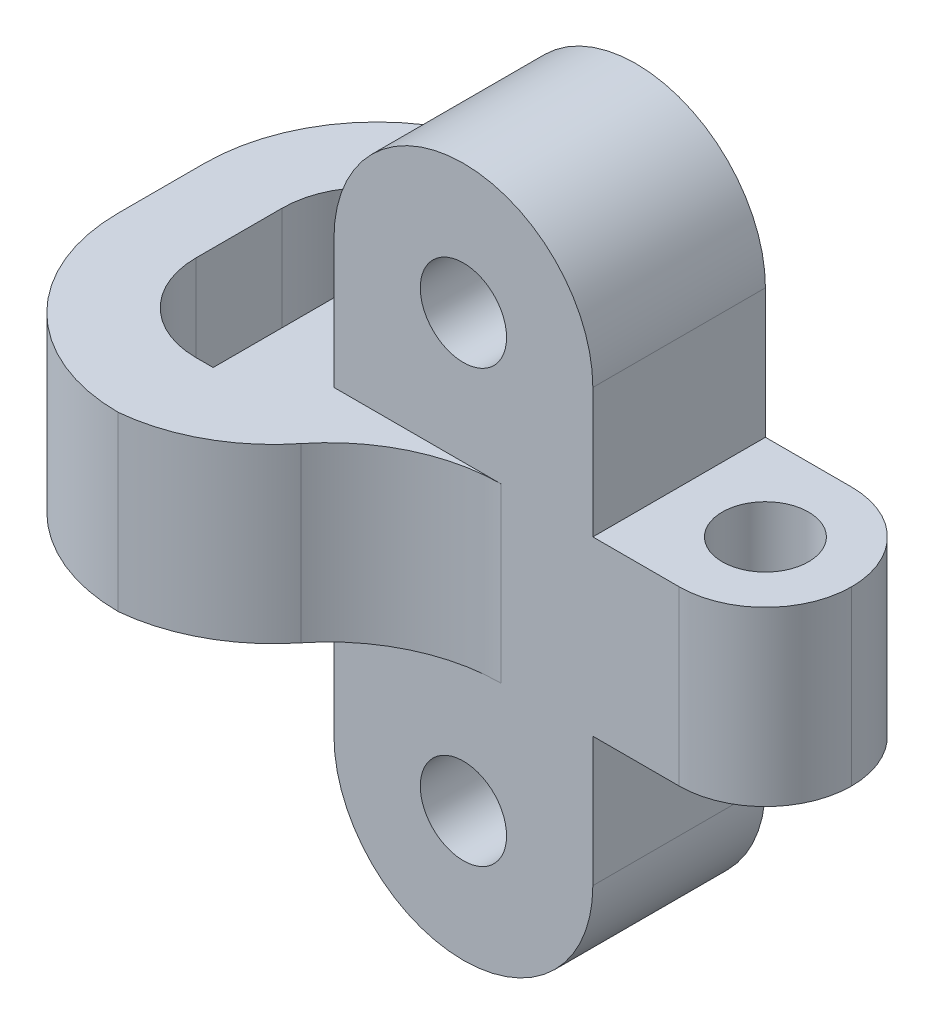
SolidWorks part; units mm, degrees
ref_plane "前视基准面" through (0, 0, 0) normal (0, 0, 1) x (1, 0, 0)
ref_plane "上视基准面" through (0, 0, 0) normal (0, 1, 0) x (1, 0, 0)
ref_plane "右视基准面" through (0, 0, 0) normal (1, 0, 0) x (0, 0, -1)
other "Configuration Table"
sketch "Sketch1" plane through (0, 0, 0) normal (0, 0, 1) x (1, 0, 0)
  line L0 (0, 0) -> (0, 25) construction
  line L1 (7.5, 25) -> (7.5, 0)
  line L2 (-7.5, 25) -> (-7.5, 0)
  circle A0 centre (0, 0) radius 2.5
  circle A1 centre (0, 0) radius 7.5
  circle A2 centre (0, 25) radius 2.5
  circle A3 centre (0, 25) radius 7.5
  point P10 (-7.5, 0)
  dimension "D1" = 15
  dimension "D2" = 5
  dimension "D3" = 25
extrude "Boss-Extrude1" add sketch "Sketch1" along normal mid plane 10 contours A1 L0 A3 L2 | L0 A1 L1 A3 | A0 A1 | A3 A2 region at (5.1533, 5.1533, 0) region at (-4.2552, 12.5, 0) region at (4.2552, 12.5, 0) region at (-5.1533, 19.8467, 0)
sketch "Sketch2" plane through (-7.5, 0, 0) normal (-1, 0, 0) x (0, 0, 1)
  line L0 (0, 25) -> (0, 0) construction
  line L1 (5, 25) -> (-5, 25) construction
  line L2 (0, 0) -> (0, 12.5) construction
  line L4 (-12.5, 7.5) -> (12.5, 7.5)
  line L5 (-12.5, 7.5) -> (-12.5, 17.5)
  line L6 (-12.5, 17.5) -> (12.5, 17.5)
  line L7 (12.5, 7.5) -> (12.5, 17.5)
  line L8 (-12.5, 7.5) -> (12.5, 17.5) construction
  line L9 (-12.5, 17.5) -> (12.5, 7.5) construction
  dimension "D1" = 25
  dimension "D2" = 10
extrude "Boss-Extrude2" add sketch "Sketch2" along normal blind 15
sketch "Sketch3" plane through (0, 17.5, 0) normal (0, 1, 0) x (1, 0, 0)
  line L0 (-15, -12.5) -> (-15, 12.5) construction
  line L1 (-22.5, -12.5) -> (-7.5, -12.5) construction
  line L2 (-22.5, 12.5) -> (-7.5, 12.5) construction
  line L3 (-15, 12.5) -> (-15, 0) construction
  line L5 (-18, -7.5) -> (-12, -7.5)
  line L6 (-18, -7.5) -> (-18, 7.5)
  line L7 (-18, 7.5) -> (-12, 7.5)
  line L8 (-12, -7.5) -> (-12, 7.5)
  line L9 (-18, -7.5) -> (-12, 7.5) construction
  line L10 (-18, 7.5) -> (-12, -7.5) construction
  dimension "D1" = 6
  dimension "D2" = 15
extrude "Cut-Extrude1" cut sketch "Sketch3" against normal blind 15
fillet "Fillet1" radius 10 4 edges at (-22.5, 12.5, 12.5) (-22.5, 12.5, -12.5) (-7.5, 12.5, -5) (-7.5, 12.5, 5)
fillet "Fillet2" radius 10 2 edges at (-7.5, 12.5, -12.5) (-7.5, 12.5, 12.5)
fillet "Fillet3" radius 5 2 edges at (-18, 12.5, 7.5) (-18, 12.5, -7.5)
sketch "Sketch4" plane through (7.5, 0, 0) normal (1, 0, 0) x (0, 0, -1)
  line L0 (0, 25) -> (0, 0) construction
  line L1 (-5, 25) -> (5, 25) construction
  line L2 (0, 0) -> (0, 12.5) construction
  line L3 (8.7735, 17.5) -> (5, 17.5) construction
  line L4 (-5, 7.5) -> (5, 7.5)
  line L5 (-5, 7.5) -> (-5, 17.5)
  line L6 (-5, 17.5) -> (5, 17.5)
  line L7 (5, 7.5) -> (5, 17.5)
  line L8 (-5, 7.5) -> (5, 17.5) construction
  line L9 (-5, 17.5) -> (5, 7.5) construction
  line L10 (5, 7.5) -> (5, 17.5) construction
extrude "Boss-Extrude3" add sketch "Sketch4" along normal blind 10
fillet "Fillet4" radius 5 2 edges at (17.5, 12.5, -5) (17.5, 12.5, 5)
sketch "Sketch5" plane through (0, 17.5, 0) normal (0, 1, 0) x (1, 0, 0)
  circle A0 centre (12.5, 0) radius 2.5
  dimension "D1" = 5
extrude "Cut-Extrude2" cut sketch "Sketch5" against normal blind 10
